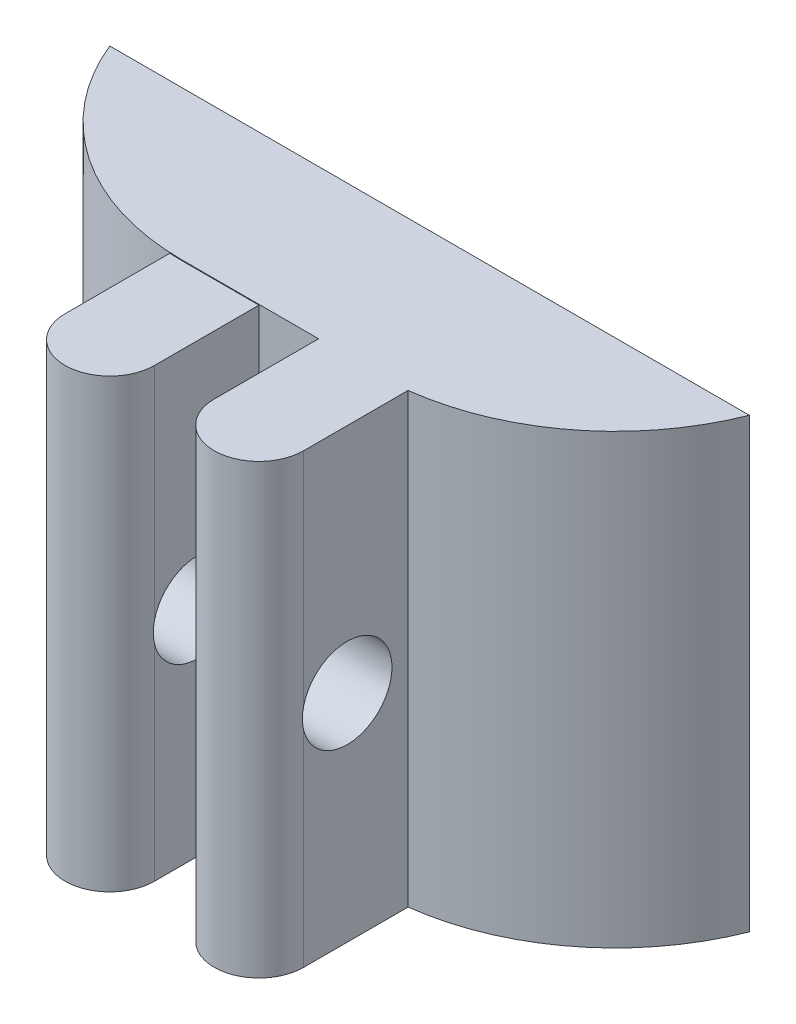
SolidWorks part; units mm, degrees
ref_plane "Front Plane" through (0, 0, 0) normal (0, 0, 1) x (1, 0, 0)
ref_plane "Top Plane" through (0, 0, 0) normal (0, 1, 0) x (1, 0, 0)
ref_plane "Right Plane" through (0, 0, 0) normal (1, 0, 0) x (0, 0, -1)
sketch "Sketch1" plane through (0, 0, 0) normal (0, 0, 1) x (1, 0, 0)
  line L1 (0, 0) -> (-22, 0)
  line L2 (0, 0) -> (0, -15)
  line L3 (0, -15) -> (-22, -15)
  line L4 (-22, 0) -> (-22, -15)
  dimension "D1" = 15
  dimension "D2" = 22
extrude "Boss-Extrude1" add sketch "Sketch1" along normal blind 5
sketch "Sketch2" plane through (0, 0, 5) normal (0, 0, 1) x (1, 0, 0)
  line L0 (0, 0) -> (-22, 0) construction
  line L1 (-10, 0) -> (-7, 0)
  line L2 (-10, 0) -> (-10, -15)
  line L3 (-10, -15) -> (-7, -15)
  line L4 (-7, 0) -> (-7, -15)
  line L5 (-22, -15) -> (0, -15) construction
  line L7 (-11, 0) -> (-11, -15) construction
  line L8 (-15, -0.0236) -> (-12, -0.0236)
  line L9 (-15, -0.0236) -> (-15, -15)
  line L10 (-15, -15) -> (-12, -15)
  line L11 (-12, -0.0236) -> (-12, -15)
  dimension "D1" = 1
  dimension "D2" = 3
  dimension "D3" = 1
  dimension "D4" = 3
extrude "Boss-Extrude2" add sketch "Sketch2" along normal blind 5
sketch "Sketch4" plane through (-12, 0, 0) normal (1, 0, 0) x (0, 0, -1)
  circle A0 centre (-7.0414, -7.7625) radius 1.5
  dimension "D1" = 3
extrude "Cut-Extrude2" cut sketch "Sketch4" against normal through all both and the other way through all
fillet "Fillet1" radius 8 2 edges at (-22, -7.5, 5) (0, -7.5, 5)
fillet "Fillet3" 2 edges at (-15, -7.5118, 10) (-12, -7.5118, 10) type full round first side face at (-15, -6.2625, 7.0414) second side face at (-12, -9.2625, 7.0414) middle face at (-13.5, -7.5118, 10)
fillet "Fillet4" 2 edges at (-10, -7.5, 10) (-7, -7.5, 10) type full round first side face at (-10, -6.2625, 7.0414) second side face at (-7, -9.2625, 7.0414) middle face at (-8.5, -7.5, 10)
